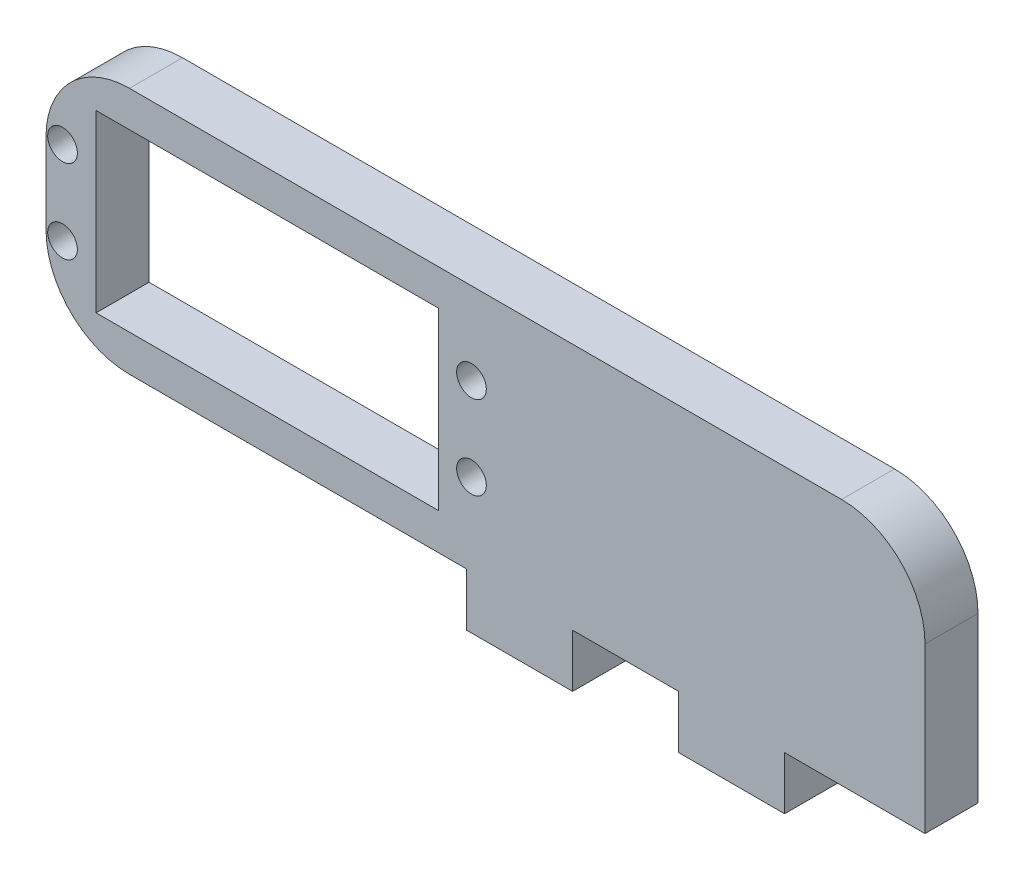
SolidWorks part; units mm, degrees
ref_plane "Front Plane" through (0, 0, 0) normal (0, 0, 1) x (1, 0, 0)
ref_plane "Top Plane" through (0, 0, 0) normal (0, 1, 0) x (1, 0, 0)
ref_plane "Right Plane" through (0, 0, 0) normal (1, 0, 0) x (0, 0, -1)
sketch "Sketch1" plane through (0, 0, 0) normal (0, 0, 1) x (1, 0, 0)
  line L0 (19.05, 38.1) -> (19.05, 44.45)
  line L1 (19.05, 44.45) -> (35.8724, 44.45)
  line L2 (38.1, 44.45) -> (-38.1, 44.45) construction
  line L3 (35.8724, 44.45) -> (35.8724, 74.1299)
  line L4 (35.8724, 74.1299) -> (-49.45, 74.1299)
  line L5 (19.05, 38.1) -> (6.35, 38.1)
  line L6 (6.35, 38.1) -> (6.35, 44.45)
  line L7 (6.35, 44.45) -> (-6.35, 44.45)
  line L8 (-6.35, 44.45) -> (-6.35, 38.1)
  line L9 (-6.35, 38.1) -> (-19.05, 38.1)
  line L10 (-19.05, 38.1) -> (-19.05, 44.45)
  line L11 (-19.05, 44.45) -> (-44.45, 44.45)
  line L12 (-44.45, 44.45) -> (-69.45, 44.45)
  line L13 (-69.45, 44.45) -> (-69.45, 74.1299)
  line L14 (-69.45, 74.1299) -> (-49.45, 74.1299)
  dimension "D1" = 20
  dimension "D2" = 25
extrude "Boss-Extrude1" add sketch "Sketch1" along normal blind 6.35
sketch "Sketch2" plane through (0, 0, 0) normal (0, 0, -1) x (-1, 0, 0)
  line L12 (-19.05, 38.1) -> (-6.35, 38.1)
  line L13 (-6.35, 38.1) -> (-6.35, 44.45)
  line L14 (-6.35, 44.45) -> (6.35, 44.45)
  line L15 (6.35, 44.45) -> (6.35, 38.1)
  line L16 (6.35, 38.1) -> (19.05, 38.1)
  line L17 (19.05, 38.1) -> (19.05, 44.45)
  line L18 (19.05, 44.45) -> (69.45, 44.45)
  line L19 (69.45, 44.45) -> (69.45, 74.1299)
  line L20 (69.45, 74.1299) -> (-35.8724, 74.1299)
  line L21 (-35.8724, 74.1299) -> (-35.8724, 44.45)
  line L22 (-35.8724, 44.45) -> (-19.05, 44.45)
  line L23 (-19.05, 44.45) -> (-19.05, 38.1)
  line L24 (-19.05, 38.1) -> (-6.35, 38.1)
  line L25 (-6.35, 38.1) -> (-6.35, 44.45)
  line L26 (-6.35, 44.45) -> (6.35, 44.45)
  line L27 (6.35, 44.45) -> (6.35, 38.1)
  line L28 (6.35, 38.1) -> (19.05, 38.1)
  line L29 (19.05, 38.1) -> (19.05, 44.45)
  line L30 (19.05, 44.45) -> (69.45, 44.45)
  line L31 (69.45, 44.45) -> (69.45, 74.1299)
  line L32 (69.45, 74.1299) -> (-35.8724, 74.1299)
  line L33 (-35.8724, 74.1299) -> (-35.8724, 44.45)
  line L34 (-35.8724, 44.45) -> (-19.05, 44.45)
  line L35 (-19.05, 44.45) -> (-19.05, 38.1)
  dimension "D1" = 0
sketch "Sketch3" plane through (0, 0, 6.35) normal (0, 0, 1) x (1, 0, 0)
  line L0 (-69.45, 44.45) -> (-69.45, 74.1299) construction
  line L1 (-63.45, 69.8299) -> (-22.45, 69.8299)
  line L2 (-63.45, 69.8299) -> (-63.45, 48.8299)
  line L3 (-63.45, 48.8299) -> (-22.45, 48.8299)
  line L4 (-22.45, 69.8299) -> (-22.45, 48.8299)
  line L5 (-69.45, 74.1299) -> (35.8724, 74.1299) construction
  circle A0 centre (-67.4705, 64.2899) radius 1.778
  circle A1 centre (-67.4705, 54.2899) radius 1.778
  circle A2 centre (-18.4705, 54.2899) radius 1.778
  circle A3 centre (-18.4705, 64.2899) radius 1.778
  dimension "D5" = 3.556
  dimension "D1" = 21
  dimension "D2" = 41
  dimension "D3" = 6
  dimension "D4" = 4.3
extrude "Cut-Extrude1" cut sketch "Sketch3" against normal through all
fillet "Fillet1" radius 10 3 edges at (-69.45, 74.1299, 3.175) (35.8724, 74.1299, 3.175) (-69.45, 44.45, 3.175)
